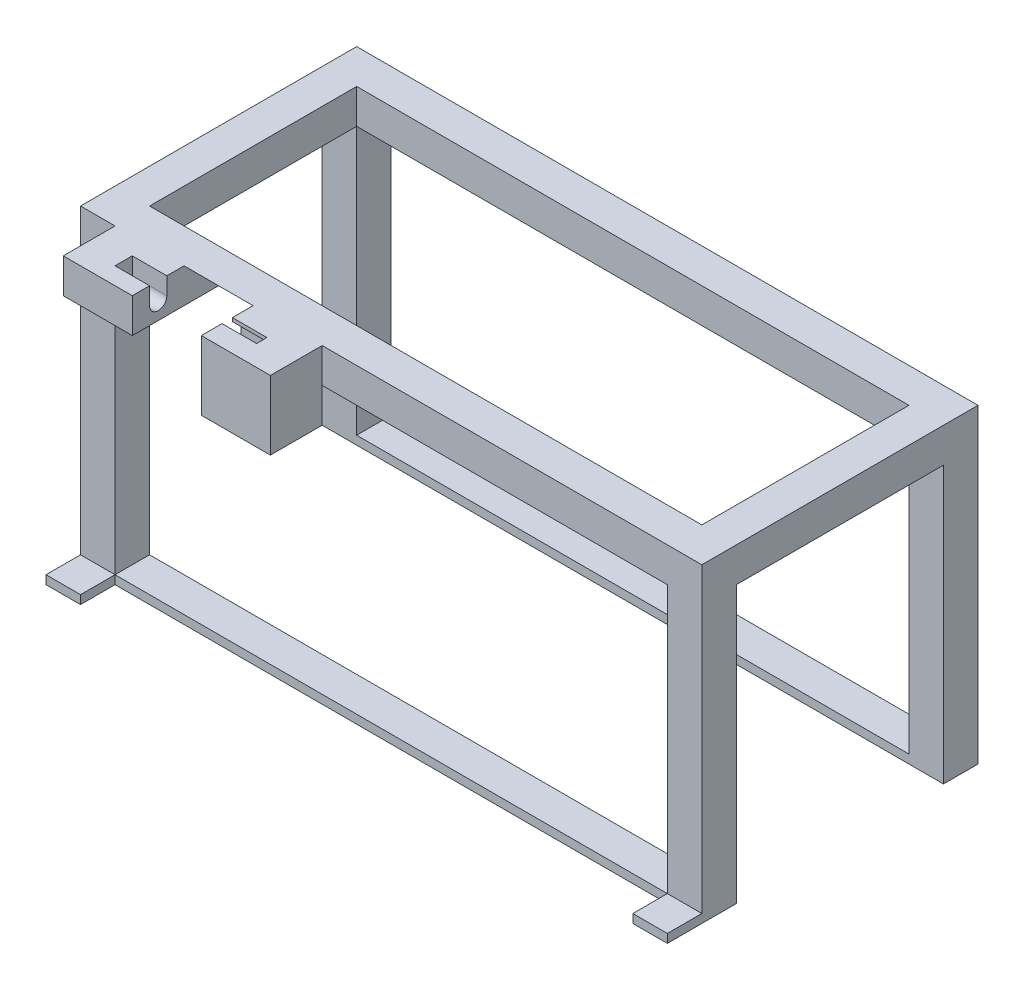
SolidWorks part; units mm, degrees
ref_plane "Front Plane" through (0, 0, 0) normal (0, 0, 1) x (1, 0, 0)
ref_plane "Top Plane" through (0, 0, 0) normal (0, 1, 0) x (1, 0, 0)
ref_plane "Right Plane" through (0, 0, 0) normal (1, 0, 0) x (0, 0, -1)
sketch "Sketch1" plane through (0, 0, 0) normal (0, 1, 0) x (1, 0, 0)
  line L0 (-203.2, 76.2) -> (-203.2, 101.6) construction
  line L1 (-203.2, -76.2) -> (203.2, -76.2)
  line L2 (-203.2, -76.2) -> (-203.2, 76.2)
  line L3 (-203.2, 76.2) -> (203.2, 76.2)
  line L4 (203.2, -76.2) -> (203.2, 76.2)
  line L5 (-203.2, -76.2) -> (203.2, 76.2) construction
  line L6 (-203.2, 76.2) -> (203.2, -76.2) construction
  line L7 (-228.6, -101.6) -> (228.6, -101.6)
  line L8 (-228.6, -101.6) -> (-228.6, 101.6)
  line L9 (-228.6, 101.6) -> (228.6, 101.6)
  line L10 (228.6, -101.6) -> (228.6, 101.6)
  line L11 (-228.6, -101.6) -> (228.6, 101.6) construction
  line L12 (-228.6, 101.6) -> (228.6, -101.6) construction
  line L13 (-203.2, 101.6) -> (-203.2, 76.2)
  line L14 (-203.2, 76.2) -> (-228.6, 76.2)
  line L15 (-228.6, -101.6) -> (-228.6, -127)
  line L16 (-228.6, -127) -> (-203.2, -127)
  line L17 (-203.2, -127) -> (-203.2, -101.6)
  line L18 (0, -125.73) -> (0, 125.73) construction
  line L19 (203.2, -127) -> (203.2, -101.6)
  line L20 (228.6, -127) -> (203.2, -127)
  line L21 (228.6, -101.6) -> (228.6, -127)
  line L22 (-203.2, -76.2) -> (-228.6, -76.2)
  line L23 (-203.2, -76.2) -> (-203.2, -101.6)
  line L24 (203.2, -76.2) -> (203.2, -101.6)
  line L25 (203.2, -76.2) -> (228.6, -76.2)
  line L26 (203.2, 76.2) -> (228.6, 76.2)
  line L27 (203.2, 101.6) -> (203.2, 76.2)
  point P0 (0, 0)
  point P6 (0, 0)
  dimension "D1" = 457.2
  dimension "D2" = 25.4
  dimension "D3" = 152.4
extrude "Boss-Extrude1" add sketch "Sketch1" along normal blind 6.35 separate body contours L23 L22 L8 L7 | L16 L17 L7 L15 | L24 L1 L23 L7 | L25 L24 L7 L10 | L21 L7 L19 L20 | L27 L9 L13 L3 region at (-215.9, 0, 88.9) region at (0, 0, 88.9) region at (215.9, 0, 88.9) region at (0, 0, -88.9) region at (-215.9, 0, 114.3) region at (215.9, 0, 114.3)
extrude "Boss-Extrude2" add sketch "Sketch1<4>" along normal blind 228.6 contours L23 L22 L8 L7 | L25 L24 L7 L10 | L9 L27 L26 L10 | L14 L13 L9 L8 region at (-215.9, 0, 88.9) region at (215.9, 0, 88.9) region at (-215.9, 0, -88.9) region at (215.9, 0, -88.9)
sketch "Sketch1<4>" plane through (0, 0, 0) normal (0, 1, 0) x (1, 0, 0) same geometry as "Sketch1"
extrude "Boss-Extrude3" add sketch "Sketch1<5>" along normal blind 25.4 from offset 203.2 contours L27 L9 L13 L3 | L24 L1 L23 L7 | L22 L2 L14 L8 | L26 L4 L25 L10 region at (-215.9, 0, 0) region at (0, 0, 88.9) region at (215.9, 0, 0) region at (0, 0, -88.9)
sketch "Sketch1<5>" plane through (0, 0, 0) normal (0, 1, 0) x (1, 0, 0) same geometry as "Sketch1"
sketch "Sketch2" plane through (0, 0, 101.6) normal (0, 0, 1) x (1, 0, 0)
  line L0 (-203.2, 203.2) -> (-203.2, 228.6)
  line L1 (-228.6, 228.6) -> (228.6, 228.6) construction
  line L2 (-203.2, 203.2) -> (-152.4, 203.2)
  line L3 (-203.2, 203.2) -> (203.2, 203.2) construction
  line L4 (-152.4, 203.2) -> (-152.4, 228.6)
  line L5 (-152.4, 228.6) -> (-203.2, 228.6)
  line L6 (-101.6, 203.2) -> (-101.6, 228.6)
  line L7 (-101.6, 228.6) -> (-50.8, 228.6)
  line L8 (-50.8, 228.6) -> (-50.8, 203.2)
  line L9 (-50.8, 203.2) -> (-101.6, 203.2)
  dimension "D1" = 50.8
  dimension "D2" = 50.8
  dimension "D3" = 50.8
extrude "Boss-Extrude4" add sketch "Sketch2" along normal blind 38.1
sketch "Sketch3" plane through (-152.4, 0, 0) normal (1, 0, 0) x (0, 0, -1)
  line L0 (-139.7, 228.6) -> (-120.65, 215.9) construction
  line L1 (-120.65, 215.9) -> (-101.6, 228.6) construction
  line L2 (-120.65, 215.9) -> (-139.7, 203.2) construction
  line L3 (-120.65, 215.9) -> (-101.6, 203.2) construction
  point P1 (-120.65, 215.9)
  point P21 (-120.65, 215.9)
hole_wizard "1/2 (0.5) Diameter Hole1" positions "Sketch3" profile "Sketch4" hole size "1/2" standard "ANSI Inch"
sketch "Sketch4" plane through (-152.4, 215.9, 120.65) normal (0, 1, 0) x (0, 0, -1)
  line L0 (0, 0) -> (0, 25.4)
  line L1 (0, 25.4) -> (6.35, 25.4)
  line L2 (6.35, 25.4) -> (6.35, 0)
  line L5 (6.35, 0) -> (0, 0)
  line L10 (0, 25.4) -> (-6.35, 25.4) construction
  line L11 (0, -6.35) -> (0, 107.95) construction
  dimension "Hole Dia." = 12.7
  dimension "Hole Depth" = 25.4
sketch "Sketch5" plane through (0, 203.2, 0) normal (0, -1, 0) x (1, 0, 0)
  line L1 (-101.6, 101.6) -> (-50.8, 101.6)
  line L2 (-101.6, 101.6) -> (-101.6, 139.7)
  line L3 (-101.6, 139.7) -> (-50.8, 139.7)
  line L4 (-50.8, 101.6) -> (-50.8, 139.7)
extrude "Boss-Extrude5" add sketch "Sketch5" along normal blind 25.4
sketch "Sketch6" plane through (-101.6, 0, 0) normal (-1, 0, 0) x (0, 0, 1)
  line L0 (130.81, 226.06) -> (139.7, 226.06) construction
  line L1 (130.81, 226.06) -> (110.49, 226.06)
  line L2 (130.81, 226.06) -> (130.81, 185.928)
  line L3 (130.81, 185.928) -> (110.49, 185.928)
  line L4 (110.49, 226.06) -> (110.49, 185.928)
  line L5 (139.7, 228.6) -> (139.7, 203.2) construction
  line L6 (110.49, 226.06) -> (101.6, 226.06) construction
  line L7 (101.6, 228.6) -> (101.6, 6.35) construction
  dimension "D1" = 10.16
  dimension "D2" = 20.32
  dimension "D3" = 40.132
extrude "Cut-Extrude1" cut sketch "Sketch6" against normal blind 27.94
sketch "Sketch7" plane through (0, 228.6, 0) normal (0, 1, 0) x (1, 0, 0)
  line L0 (-152.4, -127) -> (-152.4, -114.3) construction
  line L1 (-152.4, -127) -> (-152.4, -114.3)
  line L2 (-152.4, -127) -> (-177.8, -127)
  line L3 (-177.8, -127) -> (-177.8, -120.65)
  line L4 (-177.8, -120.65) -> (-152.4, -120.65) construction
  line L5 (-177.8, -120.65) -> (-177.8, -114.3)
  line L6 (-177.8, -114.3) -> (-152.4, -114.3)
  dimension "D1" = 25.4
extrude "Cut-Extrude2" cut sketch "Sketch7" against normal blind 12.7
sketch "Sketch8" plane through (0, 228.6, 0) normal (0, 1, 0) x (1, 0, 0)
  line L0 (-101.6, -124.46) -> (-76.2, -124.46)
  line L1 (-101.6, -139.7) -> (-101.6, -101.6) construction
  line L2 (-101.6, -120.65) -> (-76.2, -120.65) construction
  line L4 (-101.6, -116.84) -> (-76.2, -116.84)
  line L5 (-76.2, -124.46) -> (-76.2, -120.65)
  line L6 (-76.2, -120.65) -> (-76.2, -116.84)
  line L7 (-101.6, -124.46) -> (-101.6, -120.65)
  line L8 (-101.6, -120.65) -> (-101.6, -116.84)
  dimension "D1" = 7.62
  dimension "D2" = 25.4
extrude "Cut-Extrude3" cut sketch "Sketch8" against normal blind 12.7
sketch "Sketch9" plane through (-228.6, 0, 0) normal (-1, 0, 0) x (0, 0, 1)
  line L0 (76.2, 203.2) -> (101.6, 228.6)
  line L1 (101.6, 228.6) -> (101.6, 203.2)
  line L2 (101.6, 203.2) -> (76.2, 203.2)
extrude "Cut-Extrude4" cut sketch "Sketch9" against normal up to surface (127 mm away) from surface up to face at (-101.6, 211.4843, 119.1846) starting at face at (-152.4, 218.2812, 120.65)
